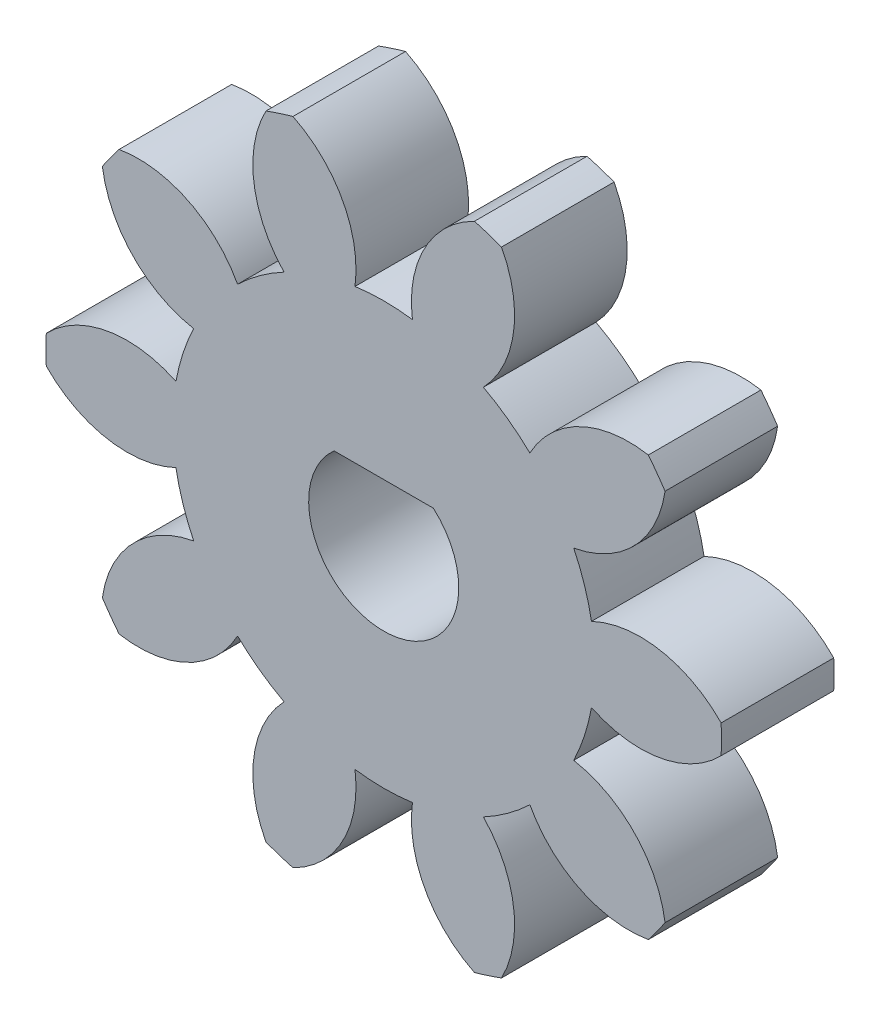
SolidWorks part; units mm, degrees
ref_plane "Front Plane" through (0, 0, 0) normal (0, 0, 1) x (1, 0, 0)
ref_plane "Top Plane" through (0, 0, 0) normal (0, 1, 0) x (1, 0, 0)
ref_plane "Right Plane" through (0, 0, 0) normal (1, 0, 0) x (0, 0, -1)
sketch "Sketch3" plane through (0, 0, 0) normal (0, 0, 1) x (1, 0, 0)
  circle A0 centre (0, 0) radius 9
  dimension "addendumDiameter" = 18
extrude "Boss-Extrude1" add sketch "Sketch3" along normal blind 3
sketch "Sketch4" plane through (0, 0, 0) normal (0, 0, -1) x (-1, 0, 0)
  line L0 (0, 0) -> (0, 30.5895) construction
  line L1 (0, 0) -> (8.5201, 26.2222) construction
  line L2 (1.1077, 7.4177) -> (2.2858, 7.035) construction
  circle A0 centre (0, 0) radius 7.5 construction
  circle A1 centre (0, 0) radius 5.625 construction
  circle A2 centre (0, 0) radius 7.0477 construction
  arc A3 (0.765, 5.5727) -> (-0.765, 5.5727) centre (0, 0) ccw
  arc A4 (-0.765, 5.5727) -> (-2.4183, 8.669) centre (-3.7379, 5.9748) ccw
  circle A8 centre (0, 0) radius 9 construction
  arc A9 (0.765, 5.5727) -> (2.4183, 8.669) centre (3.7379, 5.9748) cw
  arc A10 (2.4183, 8.669) -> (-2.4183, 8.669) centre (0, 0) ccw
  dimension "D1" = 14.0954
  dimension "D2" = 11.25
  dimension "D3" = 15
  dimension "D5" = 3
  dimension "D4" = 18
  dimension "D6" = 1.1781
extrude "Cut-Extrude1" cut sketch "Sketch4" against normal blind 3 contours A3 A4 A10 A9
pattern_circular "CirPattern1" count 10 over 360 about axis through (0, 0, 3) along (0, 0, 1) of "Cut-Extrude1"
sketch "Sketch5" [suppressed] plane through (0, 0, 3) normal (0, 0, 1) x (1, 0, 0)
  line L0 (0, 0) -> (-1.2024, 2.4935) construction
  line L1 (-1.2024, 2.4935) -> (0.3203, 10.8898)
  line L3 (-8.7205, 6.5302) -> (-1.2024, 2.4935)
  line L4 (-1.2024, 2.4935) -> (-5.9289, 12.2951) construction
  arc A0 (0.3203, 10.8898) -> (-8.7205, 6.5302) centre (0, 0) ccw
  circle A1 centre (0, 0) radius 2.704 construction
  dimension "D1" = 4.8
extrude "Cut-Extrude4" [suppressed] cut sketch "Sketch5" against normal blind 3
fillet "Fillet2" [suppressed] radius 2
ref_axis "Axis1" [suppressed] through (0, 0, 0) along (0, 0, 1)
pattern_circular "CirPattern2" [suppressed] count 4 over 360 about axis through (0, 0, 0) along (0, 0, 1) of bodies 106
sketch "Sketch6" plane through (0, 0, 0) normal (0, 0, -1) x (-1, 0, 0)
  line L0 (-1.3229, 1.5) -> (1.3229, 1.5)
  line L1 (0, 0) -> (0, 1.5) construction
  arc A0 (-1.3229, 1.5) -> (1.3229, 1.5) centre (0, 0) ccw
  dimension "D1" = 4
  dimension "D2" = 1.5
extrude "Cut-Extrude8" cut sketch "Sketch6" against normal blind 71.5
equation "\"module\"= 1.5"
equation "\"teeth\"= 10"
equation "\"pressureAngle\"= 20deg"
equation "\"gearThickness\"= 3"
equation "\"addendumFactor\"= 1"
equation "\"dedendumFactor\"= 1.25"
equation "\"pitch\"= 1 / \"module\""
equation "\"pitchDiameter\"= \"teeth\" / \"pitch\""
equation "\"addendum\"= \"addendumFactor\" / \"pitch\""
equation "\"dedendum\"= \"dedendumFactor\" / \"pitch\""
equation "\"addendumDiameter@Sketch3\"=   \"pitchDiameter\" + 2 * \"addendum\""
equation "\"D1@Boss-Extrude1\"=\"gearThickness\""
equation "\"D1@Sketch4\"=\"pitchDiameter\" * cos ( \"pressureAngle\" )"
equation "\"D2@Sketch4\"=\"pitchDiameter\" - 2 * \"dedendum\""
equation "\"D3@Sketch4\"=\"pitchDiameter\""
equation "\"D4@Sketch4\"=180/\"teeth\""
equation "\"D5@Sketch4\"=\"pitchDiameter\" / 5"
equation "\"D6@Sketch4\"=PI / 2 / \"pitch\" / 2"
equation "\"D1@CirPattern1\"=\"teeth\""
equation "\"D1@Sketch5\"= (\"pitchDiameter\" + 2 * \"addendum\")/3.75"
